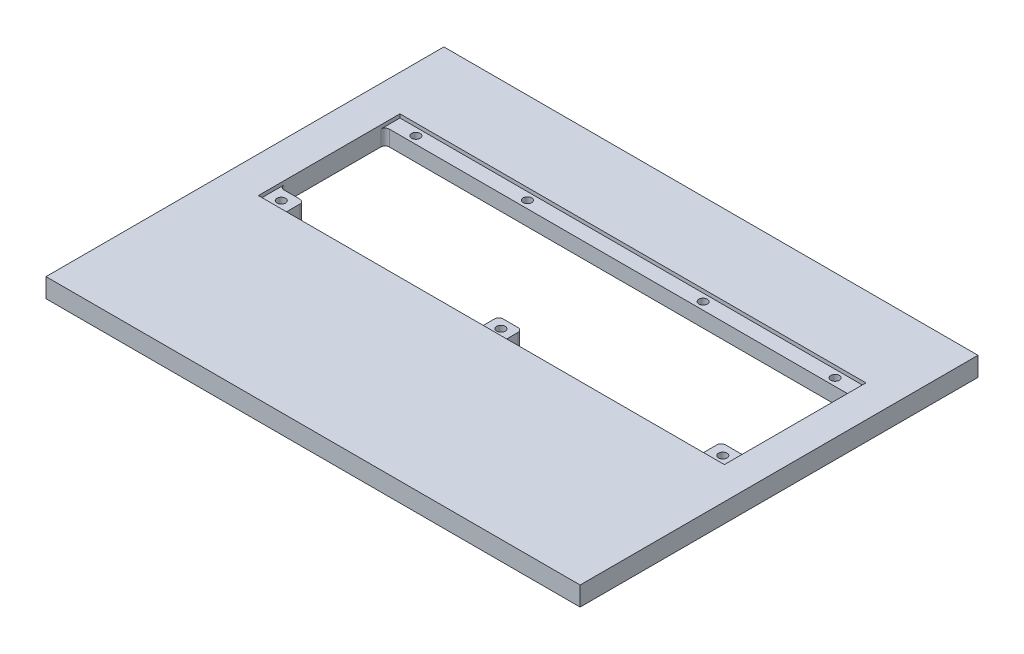
SolidWorks part; units mm, degrees
ref_plane "Front Plane" through (0, 0, 0) normal (0, 0, 1) x (1, 0, 0)
ref_plane "Top Plane" through (0, 0, 0) normal (0, 1, 0) x (1, 0, 0)
ref_plane "Right Plane" through (0, 0, 0) normal (1, 0, 0) x (0, 0, -1)
sketch "Sketch1" plane through (0, 0, 0) normal (0, 1, 0) x (1, 0, 0)
  line L1 (0, 0) -> (250.9, 0)
  line L2 (0, 0) -> (0, 186.9)
  line L3 (0, 186.9) -> (250.9, 186.9)
  line L4 (250.9, 0) -> (250.9, 186.9)
  dimension "D1" = 186.9
  dimension "D2" = 250.9
extrude "Boss-Extrude1" add sketch "Sketch1" along normal blind 9
sketch "Sketch2" plane through (0, 0, 0) normal (0, 1, 0) x (1, 0, 0)
  line L0 (250.9, 186.9) -> (0, 186.9) construction
  line L1 (16.91, 149.35) -> (235.81, 149.35)
  line L2 (16.91, 149.35) -> (16.91, 82.85)
  line L3 (16.91, 82.85) -> (235.81, 82.85)
  line L4 (235.81, 149.35) -> (235.81, 82.85)
  line L5 (250.9, 0) -> (250.9, 186.9) construction
  dimension "D1" = 37.55
  dimension "D2" = 15.09
  dimension "D3" = 66.5
  dimension "D4" = 218.9
extrude "Cut-Extrude1" cut sketch "Sketch2" along normal blind 9
sketch "Sketch3" plane through (0, 9, 0) normal (0, 1, 0) x (1, 0, 0)
  line L0 (235.81, 149.35) -> (16.91, 149.35) construction
  line L1 (16.91, 149.35) -> (16.91, 82.85) construction
  line L2 (16.91, 82.85) -> (235.81, 82.85) construction
  circle A0 centre (27.91, 145.85) radius 2
  circle A1 centre (80.31, 145.85) radius 2
  circle A2 centre (162.81, 145.85) radius 2
  circle A3 centre (224.81, 145.85) radius 2
  circle A4 centre (22.66, 87.85) radius 2
  circle A5 centre (126.36, 87.35) radius 2
  circle A6 centre (230.06, 87.85) radius 2
  dimension "D3" = 4
  dimension "D4" = 3.5
  dimension "D6" = 3.5
  dimension "D8" = 3.5
  dimension "D10" = 5
  dimension "D12" = 4.5
  dimension "D14" = 5
  dimension "D1" = 3.5
  dimension "D2" = 11
  dimension "D5" = 52.4
  dimension "D7" = 82.5
  dimension "D9" = 62
  dimension "D11" = 5.75
  dimension "D13" = 103.7
  dimension "D15" = 103.7
sketch "Sketch4" plane through (0, 0, 0) normal (0, 1, 0) x (1, 0, 0)
  line L0 (235.81, 82.85) -> (235.81, 149.35) construction
  line L1 (16.91, 149.35) -> (235.81, 149.35)
  line L2 (16.91, 149.35) -> (16.91, 142.35)
  line L3 (16.91, 142.35) -> (235.81, 142.35)
  line L4 (235.81, 149.35) -> (235.81, 142.35)
  line L5 (16.91, 82.85) -> (235.81, 82.85) construction
  line L6 (235.81, 82.85) -> (224.31, 82.85)
  line L7 (235.81, 82.85) -> (235.81, 92.85)
  line L8 (235.81, 92.85) -> (224.31, 92.85)
  line L9 (224.31, 82.85) -> (224.31, 92.85)
  line L10 (120.86, 82.85) -> (131.86, 82.85)
  line L11 (120.86, 82.85) -> (120.86, 91.85)
  line L12 (120.86, 91.85) -> (131.86, 91.85)
  line L13 (131.86, 82.85) -> (131.86, 91.85)
  line L15 (16.91, 82.85) -> (28.41, 82.85)
  line L16 (16.91, 82.85) -> (16.91, 92.85)
  line L17 (16.91, 92.85) -> (28.41, 92.85)
  line L18 (28.41, 82.85) -> (28.41, 92.85)
  dimension "D1" = 7
  dimension "D2" = 5
  dimension "D3" = 5.75
  dimension "D4" = 4.5
  dimension "D5" = 5.5
  dimension "D6" = 5.5
  dimension "D7" = 5.75
  dimension "D8" = 5
extrude "Boss-Extrude2" add sketch "Sketch4" along normal blind 7.3
extrude "Cut-Extrude2" cut sketch "Sketch3" against normal blind 6.6
fillet "Fillet1" radius 2 12 edges at (16.91, 3.65, -92.85) (28.41, 3.65, -82.85) (28.41, 3.65, -92.85) (16.91, 3.65, -142.35) (235.81, 3.65, -142.35) (235.81, 3.65, -92.85) (224.31, 3.65, -82.85) (224.31, 3.65, -92.85) (120.86, 3.65, -82.85) (131.86, 3.65, -82.85) (131.86, 3.65, -91.85) (120.86, 3.65, -91.85)
